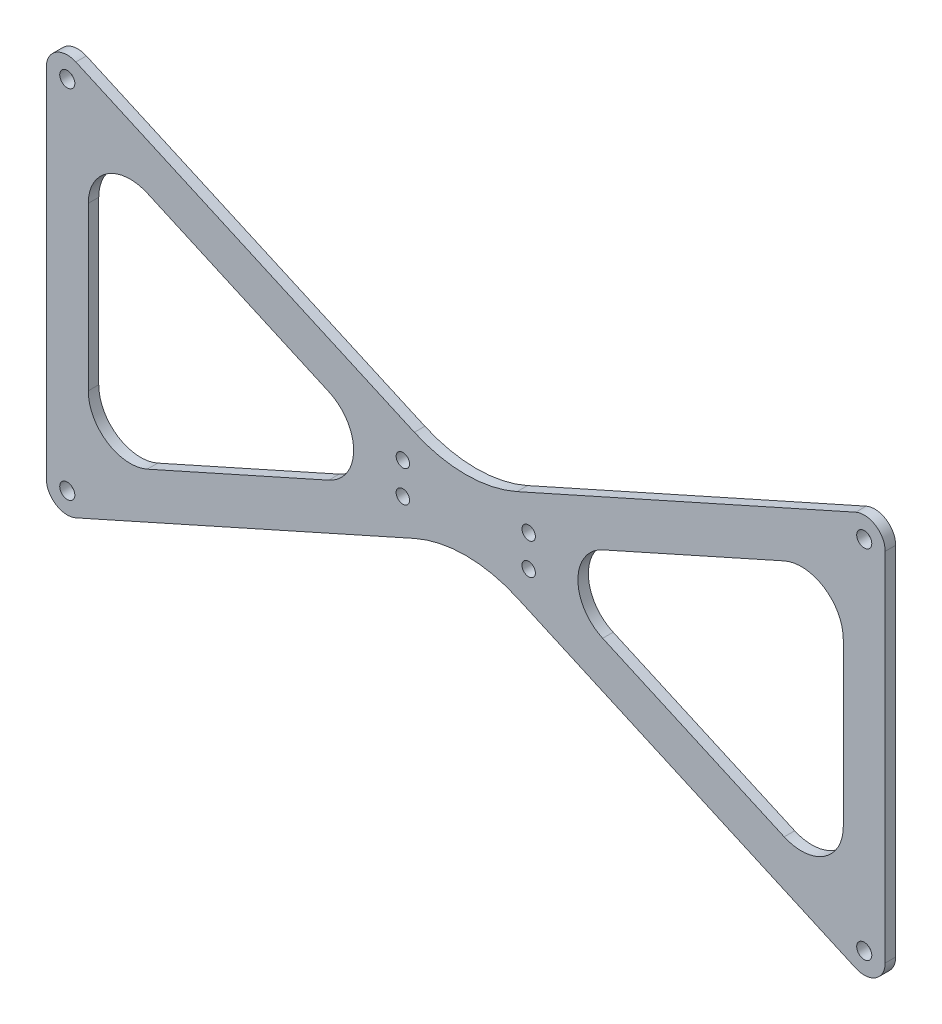
SolidWorks part; units mm, degrees
ref_plane "Front Plane" through (0, 0, 0) normal (0, 0, 1) x (1, 0, 0)
ref_plane "Top Plane" through (0, 0, 0) normal (0, 1, 0) x (1, 0, 0)
ref_plane "Right Plane" through (0, 0, 0) normal (1, 0, 0) x (0, 0, -1)
sketch "Sketch1" plane through (0, 0, 0) normal (0, 0, 1) x (1, 0, 0)
  line L0 (-120.65, -53.975) -> (120.65, 53.975) construction
  line L3 (-114.3, -44.1777) -> (-15.5498, 0)
  line L11 (-120.65, 53.975) -> (120.65, -53.975) construction
  line L12 (-118.0569, 59.7714) -> (0, 6.9565)
  line L13 (-114.3, 44.1777) -> (-15.5498, 0)
  line L14 (0, 6.9565) -> (118.0569, 59.7714)
  line L16 (15.5498, 0) -> (114.3, 44.1777)
  line L17 (15.5498, 0) -> (114.3, -44.1777)
  line L18 (-127, 53.975) -> (-127, -53.975)
  line L19 (-114.3, 44.1777) -> (-114.3, -44.1777)
  line L20 (127, 53.975) -> (127, -53.975)
  line L21 (114.3, 44.1777) -> (114.3, -44.1777)
  line L28 (-118.0569, -59.7714) -> (0, -6.9565)
  line L30 (0, -6.9565) -> (118.0569, -59.7714)
  arc A4 (-127, -53.975) -> (-118.0569, -59.7714) centre (-120.65, -53.975) ccw
  arc A5 (127, 53.975) -> (118.0569, 59.7714) centre (120.65, 53.975) ccw
  arc A6 (-118.0569, 59.7714) -> (-127, 53.975) centre (-120.65, 53.975) ccw
  arc A7 (118.0569, -59.7714) -> (127, -53.975) centre (120.65, -53.975) ccw
  point P2 (0, 0)
  point P9 (0, 0)
  point P12 (0, 0)
  point P13 (0, 0)
  point P14 (0, 0)
  point P18 (0, -6.9565)
  point P26 (0, 0)
  dimension "D1" = 254
  dimension "D3" = 6.35
  dimension "D2" = 107.95
  dimension "D5" = 12.7
extrude "Boss-Extrude1" add sketch "Sketch1" along normal blind 3.175
sketch "Sketch2" plane through (0, 0, 3.175) normal (0, 0, 1) x (1, 0, 0)
  circle A0 centre (-120.65, 53.975) radius 2.286
  circle A1 centre (-120.65, -53.975) radius 2.286
  circle A2 centre (120.65, -53.975) radius 2.286
  circle A3 centre (120.65, 53.975) radius 2.286
  arc A4 (-118.0569, 59.7714) -> (-127, 53.975) centre (-120.65, 53.975) ccw construction
  arc A5 (-127, -53.975) -> (-118.0569, -59.7714) centre (-120.65, -53.975) ccw construction
  arc A6 (118.0569, -59.7714) -> (127, -53.975) centre (120.65, -53.975) ccw construction
  arc A7 (127, 53.975) -> (118.0569, 59.7714) centre (120.65, 53.975) ccw construction
  dimension "D1" = 4.572
extrude "Cut-Extrude1" cut sketch "Sketch2" against normal through all
fillet "Fillet1" radius 12.7 6 edges at (114.3, -44.1777, 1.5875) (114.3, 44.1777, 1.5875) (15.5498, 0, 1.5875) (-114.3, -44.1777, 1.5875) (-15.5498, 0, 1.5875) (-114.3, 44.1777, 1.5875)
fillet "Fillet5" radius 38.1 2 edges at (0, -6.9565, 1.5875) (0, 6.9565, 1.5875)
sketch "Sketch5" plane through (0, 0, 3.175) normal (0, 0, 1) x (1, 0, 0)
  circle A0 centre (-19.05, 4.8799) radius 2.032
  circle A1 centre (-19.05, -4.6451) radius 2.032
  circle A2 centre (-19.05, 4.8799) radius 1.905 construction
  point P6 (0, 0)
  point P7 (-19.05, -5.4404)
  point P8 (0, 0)
  dimension "D2" = 4.064
  dimension "D1" = 9.525
extrude "Cut-Extrude3" cut sketch "Sketch5" against normal through all
mirror "Mirror1" about plane through (0, 0, 0) normal (1, 0, 0) of "Cut-Extrude3"
